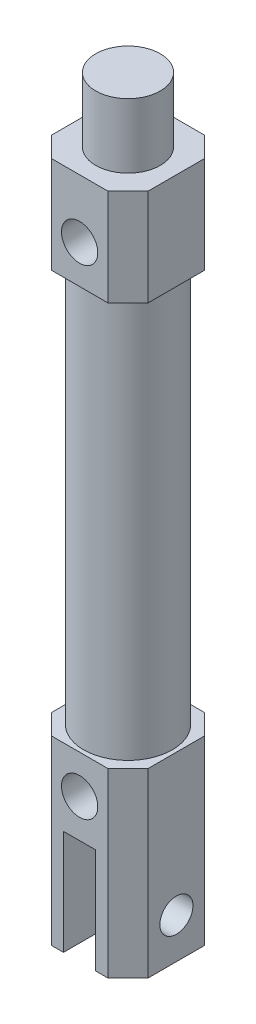
SolidWorks part; units mm, degrees
ref_plane "Front Plane" through (0, 0, 0) normal (0, 0, 1) x (1, 0, 0)
ref_plane "Top Plane" through (0, 0, 0) normal (0, 1, 0) x (1, 0, 0)
ref_plane "Right Plane" through (0, 0, 0) normal (1, 0, 0) x (0, 0, -1)
sketch "Sketch1" plane through (0, 0, 0) normal (0, 1, 0) x (1, 0, 0)
  line L1 (-6, -6) -> (6, -6)
  line L2 (-6, -6) -> (-6, 6)
  line L3 (-6, 6) -> (6, 6)
  line L4 (6, -6) -> (6, 6)
  line L5 (-6, -6) -> (6, 6) construction
  line L6 (-6, 6) -> (6, -6) construction
  point P0 (0, 0)
  dimension "D1" = 12
  dimension "D2" = 12
extrude "Boss-Extrude1" add sketch "Sketch1" along normal blind 22.5
sketch "Sketch2" plane through (0, 22.5, 0) normal (0, 1, 0) x (1, 0, 0)
  circle A0 centre (0, 0) radius 5.5
  dimension "D1" = 11
extrude "Boss-Extrude2" add sketch "Sketch2" along normal blind 50
sketch "Sketch3" plane through (0, 72.5, 0) normal (0, 1, 0) x (1, 0, 0)
  line L1 (-6, 6) -> (6, 6)
  line L2 (-6, 6) -> (-6, -6)
  line L3 (-6, -6) -> (6, -6)
  line L4 (6, 6) -> (6, -6)
  line L5 (-6, 6) -> (6, -6) construction
  line L6 (-6, -6) -> (6, 6) construction
  point P0 (0, 0)
extrude "Boss-Extrude3" add sketch "Sketch3" along normal blind 12
sketch "Sketch4" plane through (0, 84.5, 0) normal (0, 1, 0) x (1, 0, 0)
  circle A0 centre (0, 0) radius 4
  dimension "D1" = 8
extrude "Boss-Extrude4" add sketch "Sketch4" along normal blind 8
chamfer "Chamfer1" distance 2.5 angle 45 4 edges at (-6, 11.25, 6) (-6, 11.25, -6) (6, 11.25, -6) (6, 11.25, 6)
chamfer "Chamfer2" distance 2.5 angle 45 4 edges at (-6, 78.5, -6) (-6, 78.5, 6) (6, 78.5, 6) (6, 78.5, -6)
sketch "Sketch5" plane through (0, 0, 6) normal (0, 0, 1) x (1, 0, 0)
  line L0 (-3.5, 0) -> (3.5, 0) construction
  line L1 (-2, 0) -> (2, 0)
  line L2 (-2, 0) -> (-2, 13)
  line L3 (-2, 13) -> (2, 13)
  line L4 (2, 0) -> (2, 13)
  point P6 (0, 13)
  dimension "D1" = 4
  dimension "D2" = 13
extrude "Cut-Extrude1" cut sketch "Sketch5" against normal through all
sketch "Sketch6" plane through (6, 0, 0) normal (1, 0, 0) x (0, 0, -1)
  circle A0 centre (0, 5) radius 2.05
  dimension "D1" = 4.1
  dimension "D2" = 5
extrude "Cut-Extrude2" cut sketch "Sketch6" against normal through all
sketch "Sketch7" plane through (0, 0, 6) normal (0, 0, 1) x (1, 0, 0)
  line L0 (2, 13) -> (-2, 13) construction
  circle A0 centre (0, 17.75) radius 2.25
  dimension "D1" = 4.75
  dimension "D2" = 4.5
extrude "Cut-Extrude3" cut sketch "Sketch7" against normal blind 7
sketch "Sketch8" plane through (0, 0, 6) normal (0, 0, 1) x (1, 0, 0)
  line L0 (-3.5, 72.5) -> (3.5, 72.5) construction
  circle A0 centre (0, 77.25) radius 2.25
  dimension "D1" = 4.75
  dimension "D2" = 4.5
extrude "Cut-Extrude4" cut sketch "Sketch8" against normal blind 7
